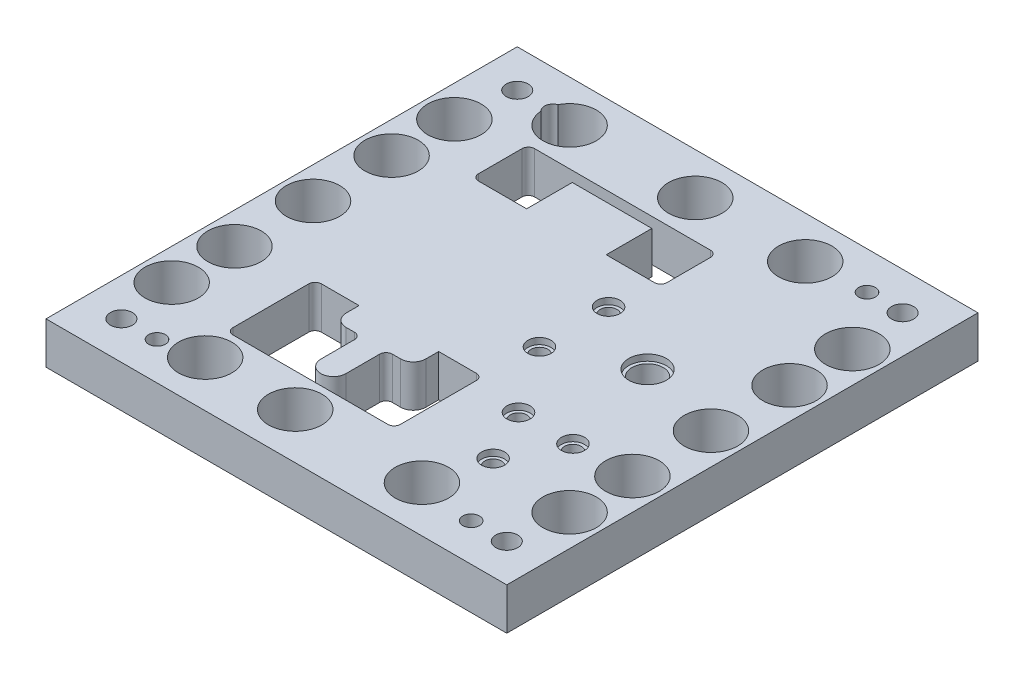
SolidWorks part; units mm, degrees
material "Plain Carbon Steel"
ref_plane "Front Plane" through (0, 0, 0) normal (0, 0, 1) x (1, 0, 0)
ref_plane "Top Plane" through (0, 0, 0) normal (0, 1, 0) x (1, 0, 0)
ref_plane "Right Plane" through (0, 0, 0) normal (1, 0, 0) x (0, 0, -1)
sketch "Sketch1" plane through (0, 0, 0) normal (0, 1, 0) x (1, 0, 0)
  line L1 (-110, -112.5) -> (110, -112.5)
  line L2 (-110, -112.5) -> (-110, 112.5)
  line L3 (-110, 112.5) -> (110, 112.5)
  line L4 (110, -112.5) -> (110, 112.5)
  line L5 (-110, -112.5) -> (110, 112.5) construction
  line L6 (-110, 112.5) -> (110, -112.5) construction
  point P0 (0, 0)
  dimension "D1" = 225
  dimension "D2" = 220
extrude "Boss-Extrude1" add sketch "Sketch1" against normal blind 20
sketch "Sketch5" plane through (0, 0, 0) normal (0, 1, 0) x (1, 0, 0)
  line L4 (-40.75, -32.27) -> (-40.75, -38.4) construction
  line L5 (-34.75, -44.4) -> (-30.75, -44.4) construction
  line L6 (-27.75, -47.4) -> (-27.75, -63.53) construction
  line L7 (-15.75, -63.53) -> (-15.75, -47.4) construction
  line L8 (-12.75, -44.4) -> (-8.75, -44.4) construction
  line L9 (-2.75, -38.4) -> (-2.75, -32.27) construction
  line L15 (-2.75, -38.4) -> (-2.75, -32.27)
  line L16 (-12.75, -44.4) -> (-8.75, -44.4)
  line L17 (-15.75, -63.53) -> (-15.75, -47.4)
  line L18 (-27.75, -47.4) -> (-27.75, -63.53)
  line L19 (-34.75, -44.4) -> (-30.75, -44.4)
  line L20 (-40.75, -32.27) -> (-40.75, -38.4)
  line L22 (-61.75, -35.27) -> (-61.75, -71.53)
  line L23 (-21.75, -63.53) -> (-21.75, -74.53) construction
  line L24 (18.25, -35.27) -> (18.25, -71.53)
  line L32 (-58.75, -74.53) -> (15.25, -74.53) construction
  line L33 (-40.75, -32.27) -> (-58.75, -32.27)
  line L34 (-2.75, -32.27) -> (15.25, -32.27)
  line L35 (15.25, -74.53) -> (-58.75, -74.53)
  line L36 (-42.75, -74.53) -> (-0.75, -74.53) construction
  arc A0 (-40.75, -38.4) -> (-34.75, -44.4) centre (-34.75, -38.4) ccw construction
  arc A1 (-27.75, -47.4) -> (-30.75, -44.4) centre (-30.75, -47.4) ccw construction
  arc A2 (-27.75, -63.53) -> (-15.75, -63.53) centre (-21.75, -63.53) ccw construction
  arc A3 (-12.75, -44.4) -> (-15.75, -47.4) centre (-12.75, -47.4) ccw construction
  arc A4 (-8.75, -44.4) -> (-2.75, -38.4) centre (-8.75, -38.4) ccw construction
  arc A5 (-8.75, -44.4) -> (-2.75, -38.4) centre (-8.75, -38.4) ccw
  arc A6 (-12.75, -44.4) -> (-15.75, -47.4) centre (-12.75, -47.4) ccw
  arc A7 (-27.75, -63.53) -> (-15.75, -63.53) centre (-21.75, -63.53) ccw
  arc A8 (-27.75, -47.4) -> (-30.75, -44.4) centre (-30.75, -47.4) ccw
  arc A9 (-40.75, -38.4) -> (-34.75, -44.4) centre (-34.75, -38.4) ccw
  arc A17 (15.25, -32.27) -> (18.25, -35.27) centre (15.25, -35.27) cw
  arc A18 (15.25, -74.53) -> (18.25, -71.53) centre (15.25, -71.53) ccw
  arc A19 (-58.75, -74.53) -> (-61.75, -71.53) centre (-58.75, -71.53) cw
  arc A20 (-58.75, -32.27) -> (-61.75, -35.27) centre (-58.75, -35.27) ccw
  point P8 (28.25, -74.53)
  point P25 (0, 0)
  point P35 (0, 0)
  dimension "D1" = 3
  dimension "D2" = 80
extrude "Cut-Extrude3" cut sketch "Sketch5" against normal up to next
sketch "Sketch6" plane through (0, 0, 0) normal (0, 1, 0) x (1, 0, 0)
  line L1 (-40.75, 47.73) -> (-45.75, 47.73) construction
  line L2 (-40.75, 69.53) -> (-40.75, 47.73) construction
  line L3 (-2.75, 69.53) -> (-40.75, 69.53) construction
  line L4 (-2.75, 47.73) -> (-2.75, 69.53) construction
  line L5 (2.25, 47.73) -> (-2.75, 47.73) construction
  line L7 (-45.75, 74.53) -> (2.25, 74.53) construction
  line L9 (-40.75, 47.73) -> (-63.75, 47.73)
  line L10 (-40.75, 69.53) -> (-40.75, 47.73)
  line L11 (-2.75, 69.53) -> (-40.75, 69.53)
  line L12 (-2.75, 47.73) -> (-2.75, 69.53)
  line L13 (20.25, 47.73) -> (-2.75, 47.73)
  line L15 (-63.75, 74.53) -> (20.25, 74.53)
  line L16 (-21.75, 69.53) -> (-21.75, 47.73) construction
  line L18 (-66.75, 50.73) -> (-66.75, 71.53)
  line L19 (23.25, 50.73) -> (23.25, 71.53)
  line L20 (-66.75, 71.53) -> (-66.75, 50.73) construction
  line L21 (23.25, 50.73) -> (23.25, 71.53) construction
  arc A0 (23.25, 71.53) -> (20.25, 74.53) centre (20.25, 71.53) ccw
  arc A1 (23.25, 50.73) -> (20.25, 47.73) centre (20.25, 50.73) cw
  arc A2 (-66.75, 50.73) -> (-63.75, 47.73) centre (-63.75, 50.73) ccw
  arc A3 (-66.75, 71.53) -> (-63.75, 74.53) centre (-63.75, 71.53) cw
  dimension "D1" = 3
extrude "Cut-Extrude4" cut sketch "Sketch6" against normal up to next
sketch "Sketch7" plane through (0, 0, 0) normal (0, 1, 0) x (1, 0, 0)
  circle A3 centre (54.5, -63.53) radius 4
  circle A4 centre (67.5, -38.4) radius 4
  circle A5 centre (41.5, -38.4) radius 4
  circle A6 centre (19.38, -6.27) radius 4
  circle A7 centre (19.38, 26.73) radius 4
  dimension "D1" = 8
extrude "Cut-Extrude5" cut sketch "Sketch7" against normal up to next
sketch "Sketch9" plane through (0, 0, 0) normal (0, 1, 0) x (1, 0, 0)
  circle A0 centre (54.5, 10.23) radius 7.5
  dimension "D1" = 15
extrude "Cut-Extrude6" cut sketch "Sketch9" against normal up to next
sketch "Sketch10" plane through (0, 0, 0) normal (0, 1, 0) x (1, 0, 0)
  circle A0 centre (19.38, 26.73) radius 5.5
  circle A1 centre (19.38, -6.27) radius 5.5
  circle A2 centre (41.5, -38.4) radius 5.5
  circle A3 centre (67.5, -38.4) radius 5.5
  circle A4 centre (54.5, -63.53) radius 5.5
  dimension "D1" = 11
extrude "Cut-Extrude7" cut sketch "Sketch10" against normal blind 3
sketch "Sketch11" plane through (0, 0, 0) normal (0, 1, 0) x (1, 0, 0)
  circle A0 centre (54.5, 10.23) radius 9
  dimension "D1" = 18
extrude "Cut-Extrude8" cut sketch "Sketch11" against normal blind 3
sketch "Sketch12" plane through (0, 0, 0) normal (0, 1, 0) x (1, 0, 0)
  circle A0 centre (19.38, 26.73) radius 2.5
  circle A1 centre (19.38, -6.27) radius 2.5
  circle A2 centre (41.5, -38.4) radius 2.5
  circle A3 centre (67.5, -38.4) radius 2.5
  circle A4 centre (54.5, -63.53) radius 2.5
  dimension "D1" = 5
hole_wizard "CBORE for M10 Hex Socket Head Cap Screw1" positions "Sketch18" profile "Sketch16" counterbore size "M10" standard "ISO" end condition through all
sketch "Sketch18" plane through (0, -20, 0) normal (0, -1, 0) x (-1, 0, 0)
  line L0 (-110, 112.5) -> (110, 112.5) construction
  line L1 (-110, -112.5) -> (-110, 112.5) construction
  line L2 (110, 112.5) -> (110, -112.5) construction
  line L3 (110, -112.5) -> (-110, -112.5) construction
  point P0 (-92, 94.5)
  point P2 (92, 94.5)
  point P4 (92, -94.5)
  point P6 (-92, -94.5)
  dimension "D1" = 18
  dimension "D2" = 18
  dimension "D3" = 18
  dimension "D4" = 18
sketch "Sketch16" plane through (92, -20, -94.5) normal (1, 0, 0) x (0, 0, -1)
  line L0 (0, 0) -> (0, 20)
  line L1 (0, 20) -> (5.25, 20)
  line L3 (5.25, 20) -> (5.25, 10.6)
  line L4 (9, 10.6) -> (5.25, 10.6)
  line L5 (9, 10.6) -> (9, 0.025)
  line L6 (9, 0.025) -> (9.025, 0)
  line L7 (9.025, 0) -> (0, 0)
  line L8 (-9, 0.025) -> (-9.025, 0) construction
  line L11 (0, -6.35) -> (0, 107.95) construction
  dimension "Thru Hole Dia." = 10.5
  dimension "Thru Hole Depth" = 20
  dimension "C'Bore Dia." = 18
  dimension "C'Bore Depth" = 10.6
  dimension "Near C'Sink Dia." = 18.05
  dimension "Near C'Sink Angle" = 90
hole_wizard "Ø8.0mm Dowel Hole1" positions "Sketch21" profile "Sketch20" hole size "Ø8.0" standard "ISO" end condition through all
sketch "Sketch21" plane through (0, -20, 0) normal (0, -1, 0) x (-1, 0, 0)
  line L0 (-110, 112.5) -> (110, 112.5) construction
  line L1 (110, -112.5) -> (-110, -112.5) construction
  circle A0 centre (-92, 94.5) radius 9.025 construction
  circle A1 centre (92, 94.5) radius 9.025 construction
  point P0 (-75, 94.5)
  point P2 (75, 94.5)
  point P4 (75, -94.5)
  point P6 (-75, -94.5)
  dimension "D2" = 17
  dimension "D1" = 17
  dimension "D3" = 18
  dimension "D4" = 18
sketch "Sketch20" plane through (75, -20, -94.5) normal (1, 0, 0) x (0, 0, -1)
  line L0 (0, 0) -> (0, 20)
  line L1 (0, 20) -> (4, 20)
  line L2 (4, 20) -> (4, 0)
  line L5 (4, 0) -> (0, 0)
  line L11 (0, -6.35) -> (0, 107.95) construction
  dimension "Thru Hole Dia." = 8
  dimension "Thru Hole Depth" = 20
hole_wizard "Ø25.5 (25.5) Diameter Hole1" positions "Sketch25" profile "Sketch23" hole size "Ø25.5" standard "ISO" end condition through all
sketch "Sketch25" plane through (0, 0, 0) normal (0, 1, 0) x (1, 0, 0)
  point P0 (-65, 92.5)
  point P3 (-5, 92.5)
  point P6 (47.5, 92.5)
  point P9 (95, 67.5)
  point P12 (95, 37.5)
  point P15 (95, 0)
  point P18 (95, -37.5)
  point P21 (95, -67.5)
  point P24 (47.5, -90.5)
  point P27 (-13, -90.5)
  point P30 (-56, -90.5)
  point P33 (-95, -67.5)
  point P36 (-95, -37.5)
  point P39 (-95, 0)
  point P51 (-95, 67.5)
  point P54 (-95, 37.5)
  point P65 (0, 0)
  point P66 (0, 0)
  point P67 (0, 0)
  point P68 (0, 0)
  point P69 (0, 0)
sketch "Sketch23" plane through (-65, 0, -92.5) normal (1, 0, 0) x (0, 0, 1)
  line L0 (0, 0) -> (0, 20)
  line L1 (0, 20) -> (12.75, 20)
  line L2 (12.75, 20) -> (12.75, 0)
  line L5 (12.75, 0) -> (0, 0)
  line L11 (0, -6.35) -> (0, 107.95) construction
  dimension "Thru Hole Dia." = 25.5
  dimension "Thru Hole Depth" = 20
